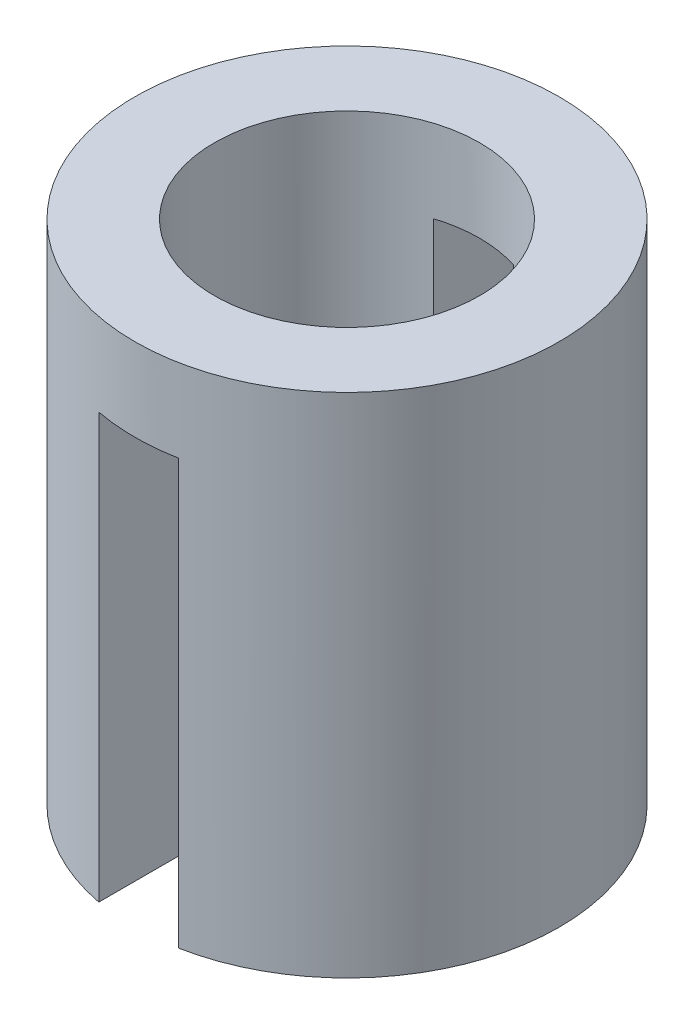
SolidWorks part; units mm, degrees
ref_plane "Front Plane" through (0, 0, 0) normal (0, 0, 1) x (1, 0, 0)
ref_plane "Top Plane" through (0, 0, 0) normal (0, 1, 0) x (1, 0, 0)
ref_plane "Right Plane" through (0, 0, 0) normal (1, 0, 0) x (0, 0, -1)
ref_axis "Axis1" through (0, -55, 0) along (0, 1, 0)
sketch "Sketch2" plane through (0, 0, 0) normal (0, 0, 1) x (1, 0, 0)
  line L0 (1.25, 0) -> (1.25, 4.78)
  line L4 (2, 4.78) -> (2, 0)
  line L5 (2, 0) -> (1.25, 0)
  line L6 (0, -55) -> (0, 55) construction
  line L7 (2, 4.78) -> (1.25, 4.78)
  dimension "D1" = 1.25
  dimension "D2" = 2
  dimension "D3" = 4.78
revolve "Revolve1" add sketch "Sketch2" angle 360 about axis through (0, -55, 0) along (0, 1, 0)
sketch "Sketch3" plane through (0, 0, 0) normal (0, 0, 1) x (1, 0, 0)
  line L0 (-2, 0) -> (2, 0) construction
  line L1 (-0.375, 0) -> (0.375, 0)
  line L2 (-0.375, 0) -> (-0.375, 4)
  line L3 (-0.375, 4) -> (0.375, 4)
  line L4 (0.375, 0) -> (0.375, 4)
  line L5 (0, -55) -> (0, 55) construction
  dimension "D1" = 0.75
  dimension "D2" = 0.375
  dimension "D3" = 4
extrude "Cut-Extrude1" cut sketch "Sketch3" against normal blind 4.78 and the other way blind 4.78
